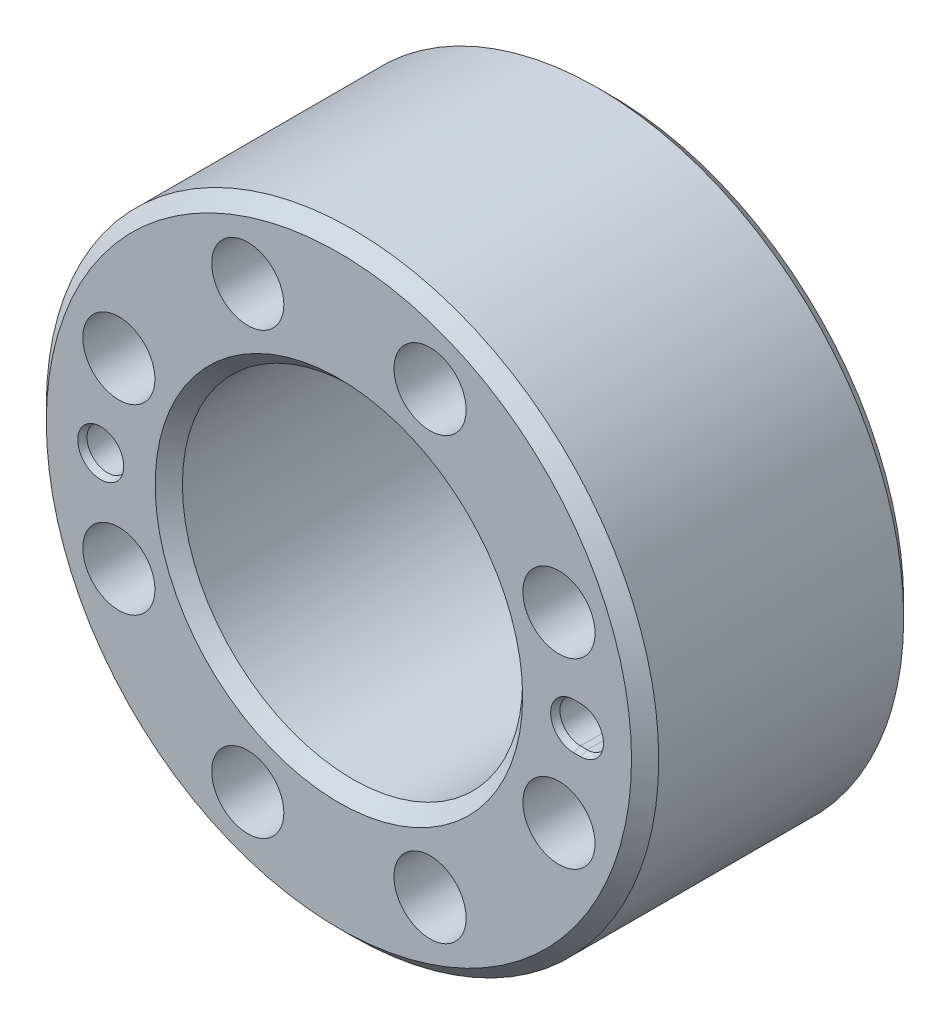
SolidWorks part; units mm, degrees
material "6061-T6 (SS)"
ref_plane "Front" through (0, 0, 0) normal (0, 0, 1) x (1, 0, 0)
ref_plane "Top" through (0, 0, 0) normal (0, 1, 0) x (1, 0, 0)
ref_plane "Right" through (0, 0, 0) normal (1, 0, 0) x (0, 0, -1)
sketch "Sketch1" plane through (0, 0, 0) normal (0, 0, 1) x (1, 0, 0)
  circle A0 centre (0, 0) radius 22.5
  circle A1 centre (0, 0) radius 12.5
  circle A2 centre (0, 0) radius 17.5 construction
  circle A3 centre (0, 17.5) radius 5 construction
  dimension "D1" = 35
  dimension "D2" = 10
  dimension "D3" = 45
  dimension "D4" = 25
extrude "Boss-Extrude1" add sketch "Sketch1" along normal mid plane 20
hole_wizard "M5 Clearance Hole1" positions "Sketch2" profile "Sketch3" hole size "M5" standard "ANSI Metric" end condition up to next
sketch "Sketch2" plane through (0, 0, 10) normal (0, 0, 1) x (1, 0, 0)
  circle A0 centre (0, 0) radius 17.5 construction
  point P0 (6.697, -16.1679)
  point P11 (16.1679, -6.697)
  point P12 (16.1679, 6.697)
  point P13 (6.697, 16.1679)
  point P14 (-6.697, 16.1679)
  point P15 (-16.1679, 6.697)
  point P16 (-16.1679, -6.697)
  point P17 (-6.697, -16.1679)
  dimension "D1" = 35
  dimension "D2" = 8
sketch "Sketch3" plane through (6.697, -16.1679, 10) normal (1, 0, 0) x (0, -1, 0)
  line L0 (0, 0) -> (0, 20)
  line L1 (0, 20) -> (2.65, 20)
  line L2 (2.65, 20) -> (2.65, 0)
  line L5 (2.65, 0) -> (0, 0)
  line L11 (0, -6.35) -> (0, 107.95) construction
  dimension "Thru Hole Dia." = 5.3
  dimension "Thru Hole Depth" = 20
hole_wizard "Ø3.0mm Clearance Dowel Hole1" positions "Sketch5" profile "Sketch4" hole size "Ø3.0" standard "ANSI Metric"
sketch "Sketch5" plane through (0, 0, 10) normal (0, 0, 1) x (1, 0, 0)
  line L0 (-17.5, 0) -> (17.5, 0) construction
  circle A0 centre (0, 0) radius 17.5 construction
  point P0 (-17.5, 0)
  point P2 (17.5, 0)
  dimension "D1" = 35
sketch "Sketch4" plane through (-17.5, 0, 10) normal (1, 0, 0) x (0, -1, 0)
  line L0 (0, 0) -> (0, 5.9061)
  line L1 (0, 5.9061) -> (1.508, 5)
  line L2 (1.508, 5) -> (1.508, 0)
  line L5 (1.508, 0) -> (0, 0)
  line L10 (0, 5.9061) -> (-1.508, 5) construction
  line L11 (0, -6.35) -> (0, 107.95) construction
  dimension "Hole Dia." = 3.016
  dimension "Hole Depth" = 5
  dimension "Drill Angle" = 118
hole_wizard "Ø2.9 (2.9) Diameter Hole1" positions "Sketch6" profile "Sketch7" hole size "Ø2.9" standard "ANSI Metric"
sketch "Sketch6" plane through (0, 0, -10) normal (0, 0, -1) x (-1, 0, 0)
  line L0 (17.5, 0) -> (-17.5, 0) construction
  circle A0 centre (0, 0) radius 17.5
  point P0 (-17.5, 0)
  point P2 (17.5, 0)
  dimension "D1" = 35
sketch "Sketch7" plane through (17.5, 0, -10) normal (1, 0, 0) x (0, 1, 0)
  line L0 (0, 0) -> (0, 7.8712)
  line L1 (0, 7.8712) -> (1.45, 7)
  line L2 (1.45, 7) -> (1.45, 0)
  line L5 (1.45, 0) -> (0, 0)
  line L10 (0, 7.8712) -> (-1.45, 7) construction
  line L11 (0, -6.35) -> (0, 107.95) construction
  dimension "Hole Dia." = 2.9
  dimension "Hole Depth" = 7
  dimension "Drill Angle" = 118
sketch "Sketch8" plane through (0, 0, 10) normal (0, 0, 1) x (1, 0, 0)
  line L0 (17.25, 0) -> (17.75, 0) construction
  line L1 (17.25, 1.508) -> (17.75, 1.508)
  line L2 (17.25, -1.508) -> (17.75, -1.508)
  arc A0 (17.25, 1.508) -> (17.25, -1.508) centre (17.25, 0) ccw
  arc A1 (17.75, -1.508) -> (17.75, 1.508) centre (17.75, 0) ccw
  circle A2 centre (17.5, 0) radius 1.508 construction
  point P2 (17.5, 0)
  dimension "D1" = 0.5
extrude "Cut-Extrude1" cut sketch "Sketch8" against normal up to vertex (4.9876 mm away)
chamfer "Chamfer1" distance 1 angle 45 4 edges at (22.5, 0, -10) (22.5, 0, 10) (12.5, 0, -10) (12.5, 0, 10)
chamfer "Chamfer2" distance 0.5 angle 20 7 edges at (16.05, 0, -10) (-18.95, 0, -10) (15.742, 0, 10) (17.5, -1.508, 10) (17.5, 1.508, 10) (19.258, 0, 10) (-15.992, 0, 10)
